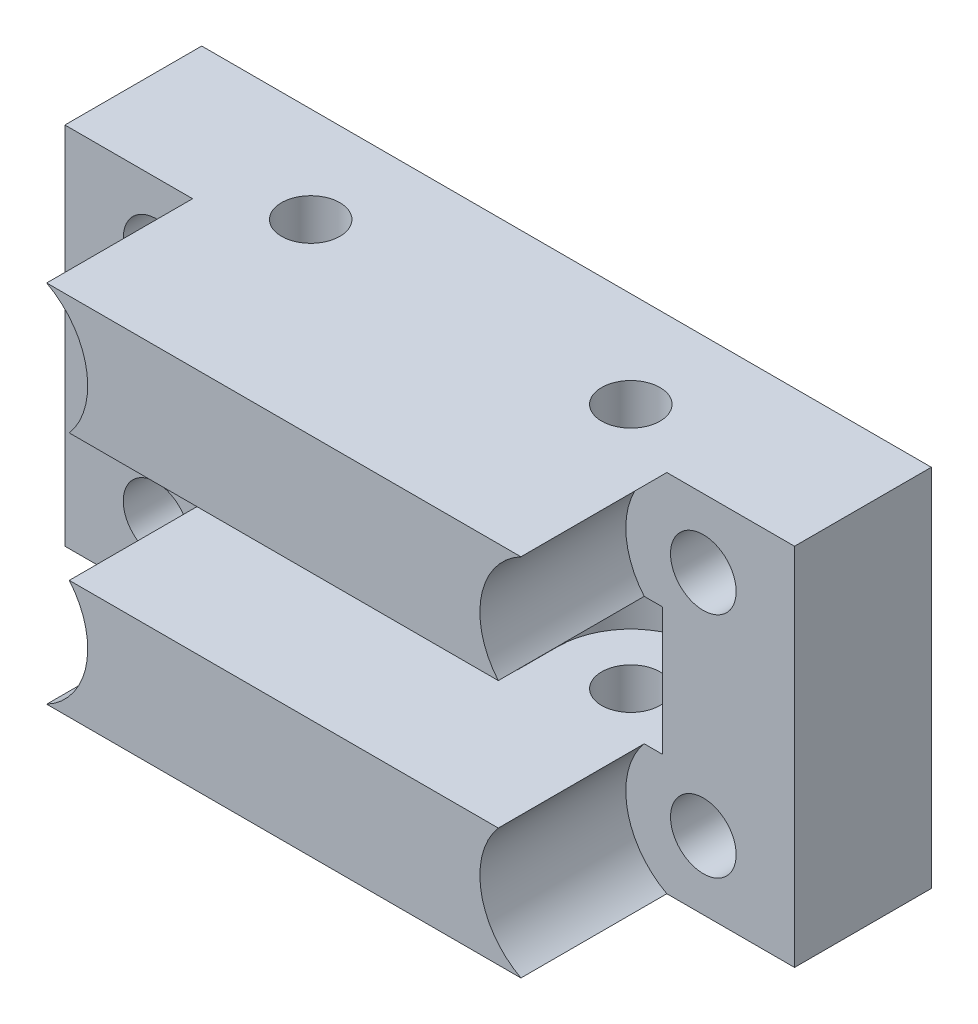
SolidWorks part; units mm, degrees
ref_plane "Front Plane" through (0, 0, 0) normal (0, 0, 1) x (1, 0, 0)
ref_plane "Top Plane" through (0, 0, 0) normal (0, 1, 0) x (1, 0, 0)
ref_plane "Right Plane" through (0, 0, 0) normal (1, 0, 0) x (0, 0, -1)
sketch "Sketch1" plane through (0, 0, 0) normal (0, 0, 1) x (1, 0, 0)
  line L0 (-25.4, 12.7) -> (25.4, -12.7) construction
  line L1 (-25.4, -12.7) -> (25.4, -12.7)
  line L2 (-25.4, -12.7) -> (-25.4, 12.7)
  line L3 (-25.4, 12.7) -> (25.4, 12.7)
  line L4 (25.4, -12.7) -> (25.4, 12.7)
  point P5 (-1.5599, -1.1583)
  point P6 (0, 0)
  dimension "D1" = 50.8
  dimension "D2" = 25.4
extrude "Boss-Extrude1" add sketch "Sketch1" along normal mid plane 9.525
sketch "Sketch2" plane through (0, 0, 4.7625) normal (0, 0, 1) x (1, 0, 0)
  line L0 (-25.4, -12.7) -> (25.4, -12.7) construction
  line L1 (-25.4, 12.7) -> (-25.4, -12.7) construction
  circle A0 centre (-19.05, 7.9375) radius 2.286
  dimension "D1" = 4.572
  dimension "D2" = 20.6375
  dimension "D3" = 6.35
extrude "Cut-Extrude1" cut sketch "Sketch2" against normal through all
sketch "Sketch4" plane through (0, 0, 0) normal (0, 1, 0) x (1, 0, 0)
  line L7 (25.4, -4.7625) -> (-25.4, -4.7625) construction
  line L8 (-16.2242, -1.905) -> (-16.2243, -4.7625)
  line L9 (-6.0642, -1.905) -> (-6.0643, -4.7625)
  line L10 (-6.0643, -4.7625) -> (-16.2243, -4.7625)
  line L11 (-25.4, -4.7625) -> (-25.4, 4.7625) construction
  arc A2 (-6.0642, -1.905) -> (-16.2242, -1.905) centre (-11.1442, -1.905) ccw
  dimension "D1" = 10.16
  dimension "D2" = 2.8575
  dimension "D3" = 14.2558
extrude "Cut-Extrude2" cut sketch "Sketch4" against normal mid plane 8.89
sketch "Sketch5" plane through (0, 12.7, 0) normal (0, 1, 0) x (1, 0, 0)
  line L0 (25.4, -4.7625) -> (-25.4, -4.7625) construction
  line L1 (-25.4, -4.7625) -> (-25.4, 4.7625) construction
  circle A0 centre (-11.1442, -1.905) radius 2.032
  dimension "D3" = 4.064
  dimension "D1" = 2.8575
  dimension "D2" = 14.2558
extrude "Cut-Extrude3" cut sketch "Sketch5" against normal through all
sketch "Sketch6" plane through (0, 0, 4.7625) normal (0, 0, 1) x (1, 0, 0)
  line L0 (-16.51, 12.7) -> (16.51, 12.7)
  line L1 (25.4, 12.7) -> (-25.4, 12.7) construction
  line L2 (-14.9347, 4.445) -> (14.9347, 4.445)
  line L3 (-16.2242, 4.445) -> (-6.0642, 4.445) construction
  arc A0 (-14.9347, 4.445) -> (-16.51, 12.7) centre (-19.05, 7.9375) ccw
  arc A1 (16.51, 12.7) -> (14.9347, 4.445) centre (19.05, 7.9375) ccw
  point P1 (0, 0)
  point P14 (-14.9347, 4.445)
  dimension "D1" = 10.795
  dimension "D2" = 38.1
  dimension "D3" = 29.8695
extrude "Boss-Extrude2" add sketch "Sketch6" along normal blind 10.16
mirror "Mirror1" about plane through (0, 0, 0) normal (0, 1, 0) of "Boss-Extrude2", "Cut-Extrude1"
mirror "Mirror2" about plane through (0, 0, 0) normal (1, 0, 0) of "Cut-Extrude3", "Mirror1", "Cut-Extrude2"
